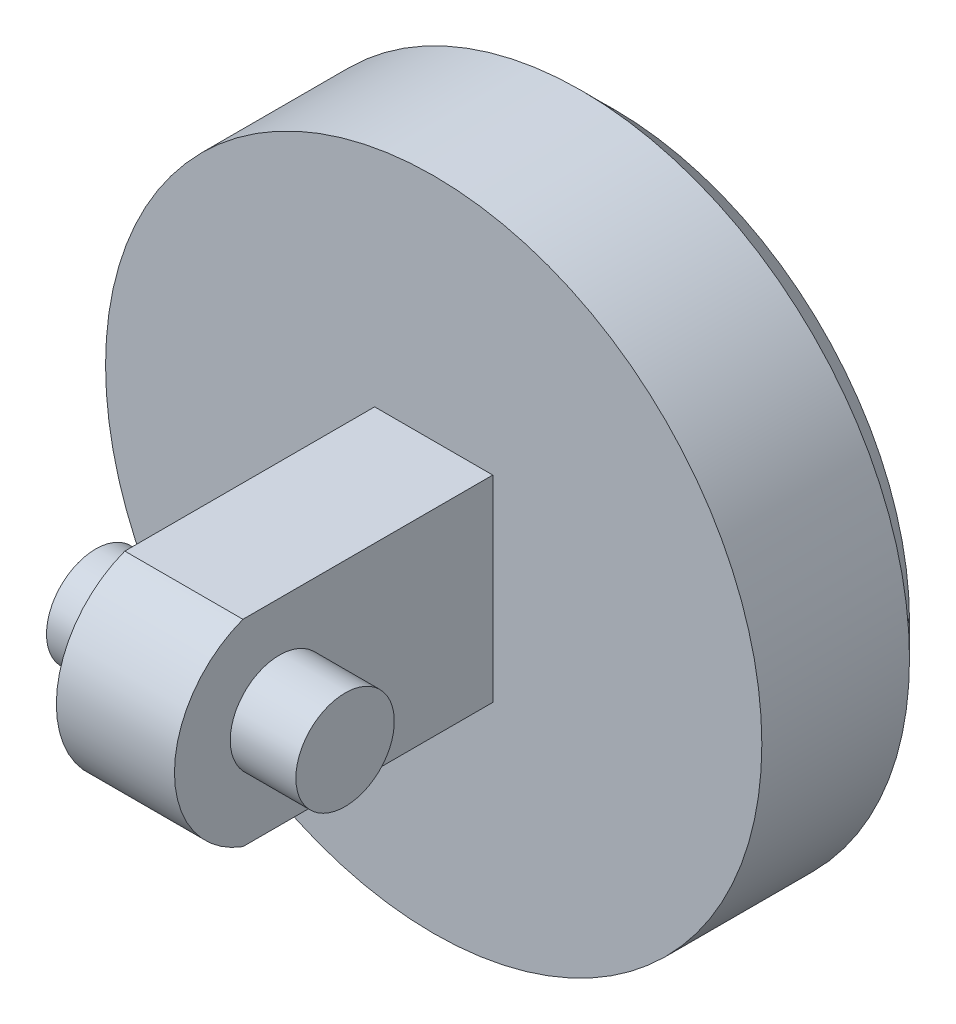
SolidWorks part; units mm, degrees
ref_plane "前视基准面" through (0, 0, 0) normal (0, 0, 1) x (1, 0, 0)
ref_plane "上视基准面" through (0, 0, 0) normal (0, 1, 0) x (1, 0, 0)
ref_plane "右视基准面" through (0, 0, 0) normal (1, 0, 0) x (0, 0, -1)
sketch "草图1" plane through (0, 0, 0) normal (0, 0, 1) x (1, 0, 0)
  circle A0 centre (0, 0) radius 10
  dimension "D1" = 20
extrude "凸台-拉伸1" add sketch "草图1" along normal blind 5.5
sketch "草图2" plane through (0, 0, 5.5) normal (0, 0, 1) x (1, 0, 0)
  line L1 (-1.8, -3) -> (1.8, -3)
  line L2 (-1.8, -3) -> (-1.8, 3)
  line L3 (-1.8, 3) -> (1.8, 3)
  line L4 (1.8, -3) -> (1.8, 3)
  line L5 (-1.8, -3) -> (1.8, 3) construction
  line L6 (-1.8, 3) -> (1.8, -3) construction
  point P0 (0, 0)
  dimension "D1" = 3.6
  dimension "D2" = 6
extrude "凸台-拉伸2" add sketch "草图2" along normal blind 9.7
sketch "草图3" plane through (-1.8, 0, 0) normal (-1, 0, 0) x (0, 0, 1)
  line L0 (15.2, 3) -> (15.2, -3) construction
  line L1 (12, -3.2) -> (12, 3.2) construction
  arc A0 (12, -3.2) -> (12, 3.2) centre (12, 0) ccw
extrude "切除-拉伸1" cut sketch "草图3" against normal through all and the other way through all flip side to cut
sketch "草图4" plane through (-1.8, 0, 0) normal (-1, 0, 0) x (0, 0, 1)
  circle A0 centre (12, 0) radius 1.5
  dimension "D1" = 3
chamfer "倒角1" distance 1 angle 45 1 edges at (10, 0, 0)
extrude "凸台-拉伸3" add sketch "草图4" along normal blind 2
mirror "镜向1" about plane through (0, 0, 0) normal (1, 0, 0) of "凸台-拉伸3"
